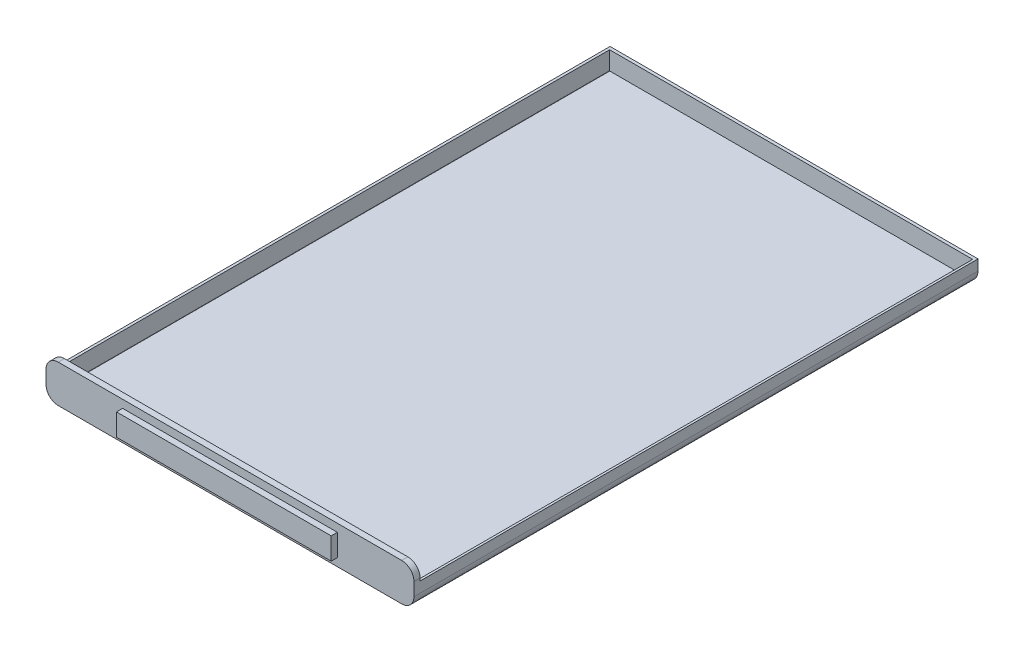
SolidWorks part; units mm, degrees
note: The reader was unsure of these and kept them because the rebuilt part matched: shared geometry of "Sketch2<2>", "Sketch3<5>", "Sketch3<6>".
material "ABS"
ref_plane "Front Plane" through (0, 0, 0) normal (0, 0, 1) x (1, 0, 0)
ref_plane "Top Plane" through (0, 0, 0) normal (0, 1, 0) x (1, 0, 0)
ref_plane "Right Plane" through (0, 0, 0) normal (1, 0, 0) x (0, 0, -1)
sketch "Sketch2" plane through (0, 0, 0) normal (0, 1, 0) x (1, 0, 0)
  line L4 (30.9606, 48.273) -> (-28.272, 48.273)
  line L5 (-28.272, -42.727) -> (-28.272, 48.273)
  line L10 (30.9606, -42.727) -> (-28.272, -42.727)
  line L11 (31.4606, -43.227) -> (-28.772, -43.227)
  line L12 (31.4606, -43.227) -> (31.4606, 48.773)
  line L13 (31.4606, 48.773) -> (-28.772, 48.773)
  line L14 (-28.772, -43.227) -> (-28.772, 48.773)
  line L15 (30.9606, -42.727) -> (30.9606, 48.273)
  point P0 (0, 0)
  point P28 (-41.1127, 3.5467)
  point P29 (19.1199, -37.6724)
  dimension "D1" = 0.5
extrude "Boss-Extrude1" add sketch "Sketch2" along normal blind 3
extrude "Boss-Extrude2" add sketch "Sketch2<2>" against normal blind 1 contours L14 L13 L12 L11
sketch "Sketch2<2>" plane through (0, 0, 0) normal (0, 1, 0) x (1, 0, 0) same geometry as "Sketch2"
sketch "Sketch3" plane through (0, 0, 43.227) normal (0, 0, 1) x (1, 0, 0)
  line L0 (29.32, 5.4077) -> (-26.6995, 5.4077)
  line L1 (31.32, 3.4077) -> (31.32, 1.264)
  line L2 (29.32, -0.736) -> (-26.6995, -0.736)
  line L3 (-28.6995, 3.4077) -> (-28.6995, 1.264)
  line L4 (31.32, 5.4077) -> (-28.6995, -0.736) construction
  line L5 (31.32, -0.736) -> (-28.6995, 5.4077) construction
  line L6 (18.82, 4.1262) -> (-16.1995, 4.1262)
  line L7 (18.82, 4.1262) -> (18.82, 0.5435)
  line L8 (18.82, 0.5435) -> (-16.1995, 0.5435)
  line L9 (-16.1995, 4.1262) -> (-16.1995, 0.5435)
  arc A0 (31.32, 1.264) -> (29.32, -0.736) centre (29.32, 1.264) cw
  arc A1 (29.32, 5.4077) -> (31.32, 3.4077) centre (29.32, 3.4077) cw
  arc A2 (-26.6995, -0.736) -> (-28.6995, 1.264) centre (-26.6995, 1.264) cw
  arc A3 (-26.6995, 5.4077) -> (-28.6995, 3.4077) centre (-26.6995, 3.4077) ccw
  point P4 (1.3103, 2.3358)
  point P21 (0, 0)
  point P22 (0, 0)
extrude "Boss-Extrude3" add sketch "Sketch3" along normal blind 1 contours L9 L8 L7 L6
extrude "Boss-Extrude5" add sketch "Sketch3<5>" against normal blind 1 contours L0 A3 L3 A2 L2 A0 L1 A1
sketch "Sketch3<5>" plane through (0, 0, 43.227) normal (0, 0, 1) x (1, 0, 0) same geometry as "Sketch3"
extrude "Cut-Extrude2" cut sketch "Sketch3<6>" against normal through all
sketch "Sketch3<6>" plane through (0, 0, 43.227) normal (0, 0, 1) x (1, 0, 0) same geometry as "Sketch3"
